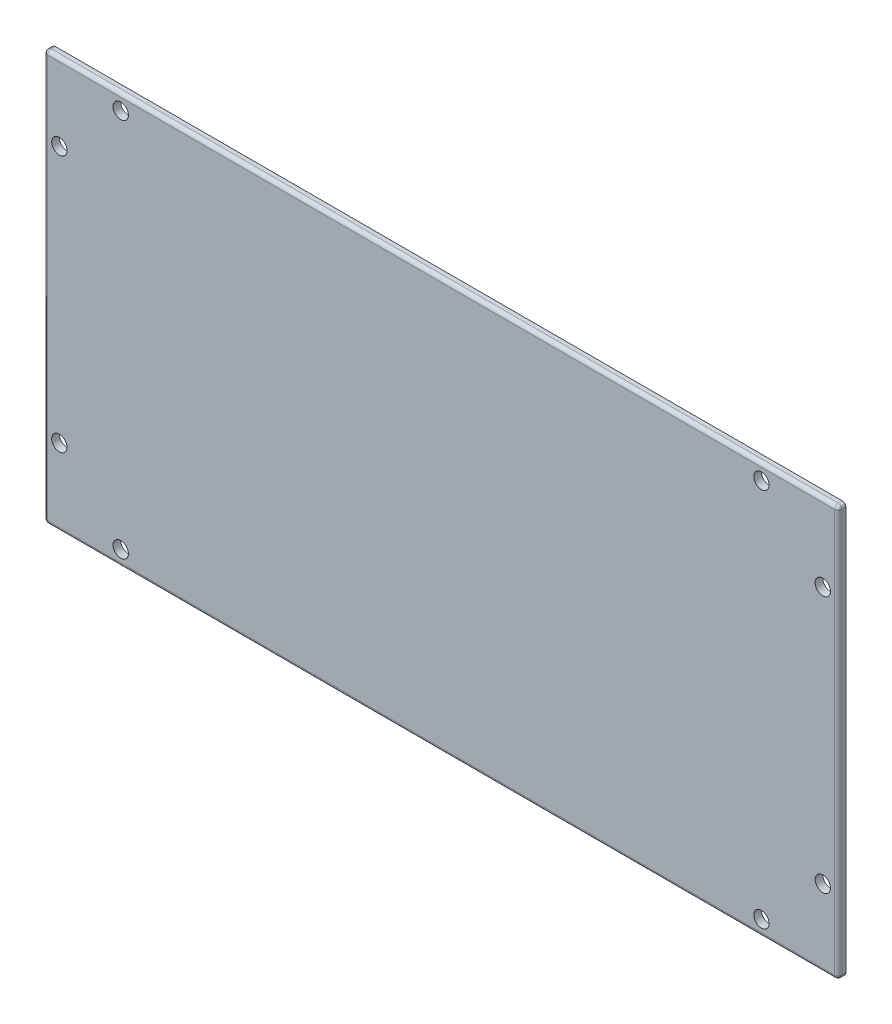
SolidWorks part; units mm, degrees
material "Teak"
ref_plane "Front Plane" through (0, 0, 0) normal (0, 0, 1) x (1, 0, 0)
ref_plane "Top Plane" through (0, 0, 0) normal (0, 1, 0) x (1, 0, 0)
ref_plane "Right Plane" through (0, 0, 0) normal (1, 0, 0) x (0, 0, -1)
sketch "Sketch1" plane through (0, 0, 0) normal (0, 0, 1) x (1, 0, 0)
  line L0 (0, 0) -> (0, 50000) construction
  line L1 (-517.4625, -267.4625) -> (517.4625, -267.4625)
  line L2 (-517.4625, -267.4625) -> (-517.4625, 267.4625)
  line L3 (-517.4625, 267.4625) -> (517.4625, 267.4625)
  line L4 (517.4625, -267.4625) -> (517.4625, 267.4625)
  line L5 (-517.4625, -267.4625) -> (517.4625, 267.4625) construction
  line L6 (-517.4625, 267.4625) -> (517.4625, -267.4625) construction
  line L7 (0, 0) -> (50000, 0) construction
  line L8 (0, 0) -> (-50000, 0) construction
  circle A0 centre (-417.4625, 247.4625) radius 10
  circle A1 centre (-497.4625, 167.4625) radius 10
  circle A2 centre (497.4625, 167.4625) radius 10
  circle A3 centre (417.4625, 247.4625) radius 10
  circle A4 centre (417.4625, -247.4625) radius 10
  circle A5 centre (497.4625, -167.4625) radius 10
  circle A6 centre (-417.4625, -247.4625) radius 10
  circle A7 centre (-497.4625, -167.4625) radius 10
  point P0 (0, 0)
  dimension "D3" = 20
  dimension "D4" = 20
  dimension "D1" = 1034.925
  dimension "D2" = 534.925
  dimension "D5" = 100
  dimension "D6" = 100
  dimension "D7" = 20
  dimension "D8" = 20
extrude "Boss-Extrude1" add sketch "Sketch1" along normal blind 10 contours L2 L3 L4 L1
fillet "Fillet1" radius 4.76 4 edges at (-517.4625, 0, 10) (0, 267.4625, 10) (517.4625, 0, 10) (0, -267.4625, 10)
fillet "Fillet2" radius 4.76 8 edges at (516.0683, -266.0683, 8.6058) (-516.0683, 266.0683, 8.6058) (-516.0683, -266.0683, 8.6058) (516.0683, 266.0683, 8.6058) (517.4625, -267.4625, 2.62) (-517.4625, 267.4625, 2.62) (-517.4625, -267.4625, 2.62) (517.4625, 267.4625, 2.62)
hole_wizard "Ø20.0mm Dowel Hole1" positions "Sketch2" profile "Sketch3" hole size "Ø20.0" standard "ANSI Metric" end condition through all
sketch "Sketch2" plane through (0, 0, 0) normal (0, 0, -1) x (-1, 0, 0)
  line L0 (-517.4625, -262.7025) -> (-517.4625, 262.7025) construction
  line L1 (512.7025, 267.4625) -> (-512.7025, 267.4625) construction
  point P0 (-417.4625, 247.4625)
  point P2 (-497.4625, 167.4625)
  dimension "D1" = 100
  dimension "D2" = 100
  dimension "D3" = 20
  dimension "D4" = 20
sketch "Sketch3" plane through (417.4625, 247.4625, 0) normal (1, 0, 0) x (0, 1, 0)
  line L0 (0, 0) -> (0, 10)
  line L1 (0, 10) -> (10, 10)
  line L2 (10, 10) -> (10, 0)
  line L5 (10, 0) -> (0, 0)
  line L11 (0, -6.35) -> (0, 107.95) construction
  dimension "Thru Hole Dia." = 20
  dimension "Thru Hole Depth" = 10
mirror "Mirror1" about plane through (0, 0, 0) normal (0, 1, 0) of "Ø20.0mm Dowel Hole1"
mirror "Mirror2" about plane through (0, 0, 0) normal (1, 0, 0) of "Mirror1"
